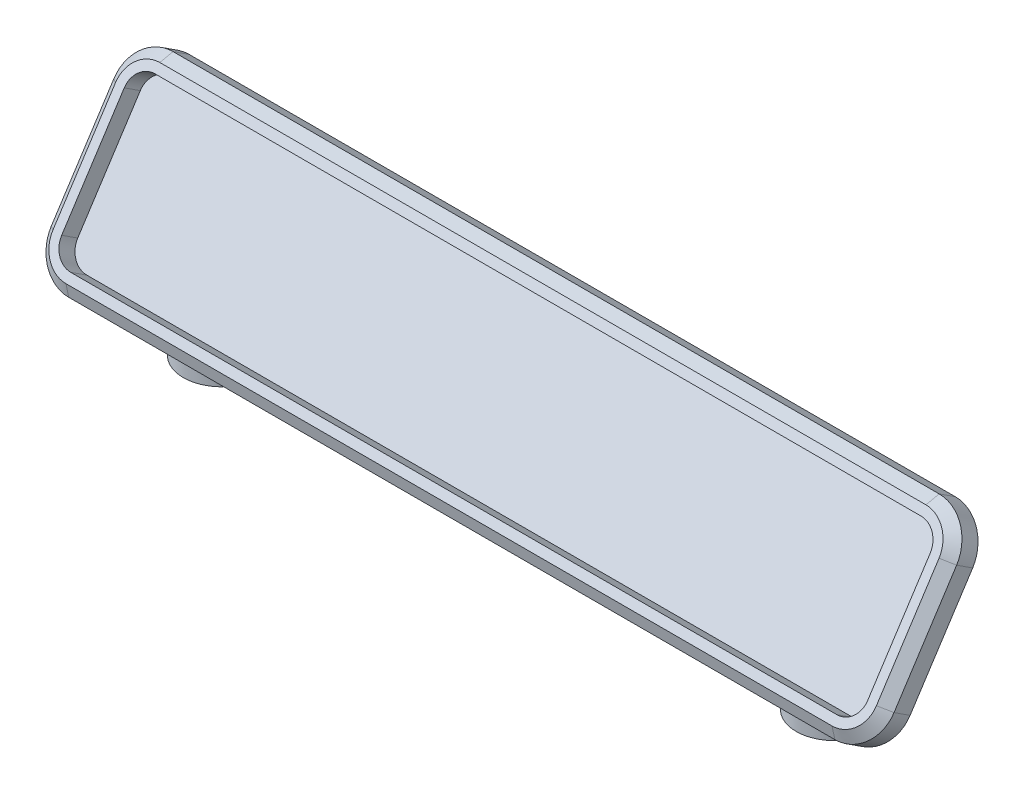
SolidWorks part; units mm, degrees
ref_plane "Front Plane" through (0, 0, 0) normal (0, 0, 1) x (1, 0, 0)
ref_plane "Top Plane" through (0, 0, 0) normal (0, 1, 0) x (1, 0, 0)
ref_plane "Right Plane" through (0, 0, 0) normal (1, 0, 0) x (0, 0, -1)
sketch "Sketch2" plane through (0, 0, 0) normal (0, 1, 0) x (1, 0, 0)
  line L0 (50.8, 0) -> (-50.8, 0) construction
  circle A0 centre (-50.8, 0) radius 6.35
  circle A1 centre (50.8, 0) radius 6.35
  point P8 (0, 0)
  dimension "D2" = 12.7
  dimension "D1" = 101.6
extrude "Boss-Extrude1" add sketch "Sketch2" along normal blind 19.05
ref_plane "Plane1" through (0, 19.05, 0) normal (0, 1, 0) x (1, 0, 0)
ref_axis "Axis1" through (88.99, 19.05, 0) along (-1, 0, 0)
ref_plane "Plane2" through (0, 5.6508, 8.7015) normal (0, 0.5446, 0.8387) x (-1, 0, 0)
sketch "Sketch3" plane through (0, 5.6508, 8.7015) normal (0, 0.5446, 0.8387) x (-1, 0, 0)
  line L0 (-50.8, -15.9767) -> (50.8, -15.9767)
  line L2 (-63.5, -31.8517) -> (63.5, -31.8517)
  line L3 (-69.85, -25.5017) -> (-69.85, -6.4517)
  line L4 (-63.5, -0.1017) -> (63.5, -0.1017)
  line L5 (69.85, -25.5017) -> (69.85, -6.4517)
  line L6 (-69.85, -31.8517) -> (69.85, -0.1017) construction
  line L7 (-69.85, -0.1017) -> (69.85, -31.8517) construction
  arc A0 (-63.5, -31.8517) -> (-69.85, -25.5017) centre (-63.5, -25.5017) cw
  arc A1 (63.5, -31.8517) -> (69.85, -25.5017) centre (63.5, -25.5017) ccw
  arc A2 (63.5, -0.1017) -> (69.85, -6.4517) centre (63.5, -6.4517) cw
  arc A3 (-69.85, -6.4517) -> (-63.5, -0.1017) centre (-63.5, -6.4517) cw
  ellipse E0 centre (50.8, -15.9767) end of major axis (44.45, -15.9767) minor radius 3.4585 construction
  ellipse E1 centre (-50.8, -15.9767) end of major axis (-57.15, -15.9767) minor radius 3.4585 construction
  ellipse E2 centre (50.8, -15.9767) end of major axis (44.45, -15.9767) minor radius 3.4585 construction
  ellipse E3 centre (-50.8, -15.9767) end of major axis (-57.15, -15.9767) minor radius 3.4585 construction
  point P22 (0, -15.9767)
  dimension "D3" = 6.35
  dimension "D1" = 139.7
  dimension "D2" = 31.75
extrude "Boss-Extrude2" add sketch "Sketch3" along normal blind 6.35 contours L2 L5 L4 L3 region at (66.9771, 29.9545, -7.0815)
sketch "Sketch8" plane through (0, 19.05, 0) normal (0, 1, 0) x (1, 0, 0)
  line L0 (44.45, 0) -> (57.15, 0) construction
  line L1 (-57.15, 0) -> (-44.45, 0) construction
  line L2 (44.45, 0) -> (57.15, 0)
  line L3 (-57.15, 0) -> (-44.45, 0)
  arc A0 (57.15, 0) -> (44.45, 0) centre (50.8, 0) ccw construction
  arc A1 (-44.45, 0) -> (-57.15, 0) centre (-50.8, 0) ccw construction
  arc A2 (57.15, 0) -> (44.45, 0) centre (50.8, 0) ccw
  arc A3 (-44.45, 0) -> (-57.15, 0) centre (-50.8, 0) ccw
  arc M1 (-44.45, 0) -> (-57.15, 0) centre (-50.8, 0) ccw
  line M2 (-57.15, 0) -> (-44.45, 0)
extrude "Boss-Extrude3" add sketch "Sketch8" along normal up to next contours L2 A2 | M2 M1 region at (50.8, 19.05, -2.695) region at (-50.8, 19.05, -2.695)
sketch "Sketch9" plane through (0, 9.1093, 14.0271) normal (0, 0.5446, 0.8387) x (1, 0, 0)
  line L8 (63.5, 28.8037) -> (-63.5, 28.8037)
  line L9 (-66.802, 25.5017) -> (-66.802, 6.4517)
  line L10 (-63.5, 3.1497) -> (63.5, 3.1497)
  line L11 (66.802, 6.4517) -> (66.802, 25.5017)
  line L12 (63.5, 28.8037) -> (-63.5, 28.8037)
  line L13 (-66.802, 25.5017) -> (-66.802, 6.4517)
  line L14 (-63.5, 3.1497) -> (63.5, 3.1497)
  line L15 (66.802, 6.4517) -> (66.802, 25.5017)
  arc A8 (63.5, 3.1497) -> (66.802, 6.4517) centre (63.5, 6.4517) ccw
  arc A9 (63.5, 3.1497) -> (66.802, 6.4517) centre (63.5, 6.4517) ccw
  arc A10 (66.802, 25.5017) -> (63.5, 28.8037) centre (63.5, 25.5017) ccw
  arc A11 (66.802, 25.5017) -> (63.5, 28.8037) centre (63.5, 25.5017) ccw
  arc A12 (-63.5, 28.8037) -> (-66.802, 25.5017) centre (-63.5, 25.5017) ccw
  arc A13 (-63.5, 28.8037) -> (-66.802, 25.5017) centre (-63.5, 25.5017) ccw
  arc A14 (-66.802, 6.4517) -> (-63.5, 3.1497) centre (-63.5, 6.4517) ccw
  arc A15 (-66.802, 6.4517) -> (-63.5, 3.1497) centre (-63.5, 6.4517) ccw
  dimension "D1" = 3.048
extrude "Cut-Extrude1" cut sketch "Sketch9" against normal blind 3.175
chamfer "Chamfer2" distance 1.5875 angle 45 16 edges at (-69.85, 19.05, 0) (0, 32.3639, -8.6461) (69.85, 19.05, 0) (0, 5.7361, 8.6461) (0, 9.1946, 13.9717) (-69.85, 22.5085, 5.3256) (69.85, 22.5085, 5.3256) (0, 35.8224, -3.3206) (67.9901, 30.8041, -7.6332) (-67.9901, 30.8041, -7.6332) (67.9901, 7.2959, 7.6332) (-67.9901, 7.2959, 7.6332) (67.9901, 10.7544, 12.9587) (-67.9901, 10.7544, 12.9587) (67.9901, 34.2625, -2.3076) (-67.9901, 34.2625, -2.3076)
hole_wizard "Hole1" positions "3DSketch1" profile "Sketch10" legacy
sketch3d "3DSketch1"
  line L0 (-50.8, 28.8281, 0) -> (-50.8, 0, 0) construction
  line L1 (50.8, 28.8281, 0) -> (50.8, 0, 0) construction
  point P0 (-50.8, 0, 0)
  point P4 (50.8, 0, 0)
sketch "Sketch10" plane through (-50.8, 0, 0) normal (1, 0, 0) x (0, 0, -1)
  line L0 (0, 0) -> (0, 10.16)
  line L1 (0, 10.16) -> (2.8575, 10.16)
  line L2 (2.8575, 10.16) -> (2.8575, 0.6858)
  line L3 (2.8575, 0.6858) -> (3.4925, 0.6858)
  line L4 (3.4925, 0.6858) -> (3.4925, 0)
  line L5 (3.4925, 0) -> (0, 0)
  line L6 (0, 110) -> (0, -10) construction
  dimension "Diameter" = 5.715
  dimension "Depth" = 10.16
  dimension "C-Bore Diameter" = 6.985
  dimension "C-Bore Depth" = 0.6858
